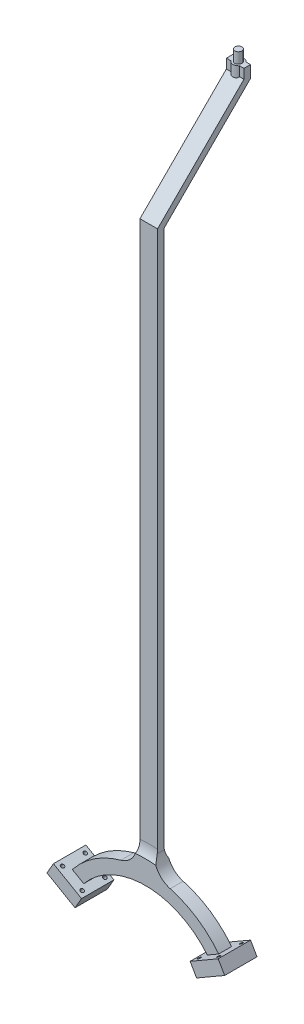
SolidWorks part; units mm, degrees
material "6063-T5"
ref_plane "Front Plane" through (0, 0, 0) normal (0, 0, 1) x (1, 0, 0)
ref_plane "Top Plane" through (0, 0, 0) normal (0, 1, 0) x (1, 0, 0)
ref_plane "Right Plane" through (0, 0, 0) normal (1, 0, 0) x (0, 0, -1)
sketch "Sketch1" plane through (0, 0, 0) normal (0, 1, 0) x (1, 0, 0)
  circle A0 centre (0, 0) radius 8.2
  dimension "D1" = 16.4
extrude "Boss-Extrude1" add sketch "Sketch1" along normal blind 25 contours A0
sketch "Sketch2" plane through (0, 0, 0) normal (0, -1, 0) x (-1, 0, 0)
  line L0 (-20.395, -7.5) -> (20.395, -7.5)
  line L1 (-20.395, -7.5) -> (-20.395, 7.5)
  line L2 (20.395, -7.5) -> (20.395, 7.5)
  line L3 (-20.395, 7.5) -> (20.395, 7.5)
  line L4 (-20.395, -7.5) -> (20.395, 7.5) construction
  line L5 (20.395, -7.5) -> (-20.395, 7.5) construction
  point P1 (0, 0)
  dimension "D1" = 40.79
  dimension "D2" = 15
extrude "Boss-Extrude2" add sketch "Sketch2" along normal blind 25
sketch "Sketch3" plane through (0, -25, 0) normal (0, -1, 0) x (-1, 0, 0)
  circle A0 centre (0, 0) radius 12.5
  dimension "D1" = 25
extrude "Boss-Extrude4" add sketch "Sketch3" against normal up to surface (25 mm away) up to face at (-13.0763, 0, 0)
sketch "Sketch4" plane through (-20.395, 0, 0) normal (-1, 0, 0) x (0, 0, 1)
  line L0 (7.5, -25) -> (207.5, -25)
  line L1 (207.5, -25) -> (207.5, -225)
  line L2 (207.5, -225) -> (7.5, -25)
  line L3 (207.5, -225) -> (192.5, -225)
  line L5 (192.5, -225) -> (-7.5, -25)
  line L6 (-7.5, -25) -> (7.5, -25)
  line M7 (-7.5, -25) -> (7.5, -25)
  dimension "D1" = 200
  dimension "D2" = 200
  dimension "D3" = 15
extrude "Boss-Extrude5" add sketch "Sketch4" against normal up to surface (40.79 mm away) contours L5 L3 L2 M7 region at (-20.395, -125, 100) up to face at (20.395, -12.5, 0)
sketch "Sketch5" plane through (0, -225, 0) normal (0, -1, 0) x (-1, 0, 0)
  line L1 (-20.395, -207.5) -> (20.395, -207.5)
  line L2 (-20.395, -207.5) -> (-20.395, -192.5)
  line L3 (-20.395, -192.5) -> (20.395, -192.5)
  line L4 (20.395, -207.5) -> (20.395, -192.5)
extrude "Boss-Extrude7" add sketch "Sketch5" along normal blind 1505
sketch "Sketch7" plane through (20.395, 0, 0) normal (1, 0, 0) x (0, 0, -1)
  line L0 (-7.5, -25) -> (0, -32.5)
  line L1 (7.5, -25) -> (-192.5, -225) construction
  line L2 (0, -32.5) -> (1.5521, -34.0521)
  line L3 (-7.5, -25) -> (-9.0521, -23.4479)
  line L4 (-9.0521, -23.4479) -> (-7.5, -21.8958)
  line L5 (-7.5, -25) -> (-7.5, 0) construction
  line L6 (1.5521, -34.0521) -> (7.5, -28.1042)
  line L7 (7.5, -28.1042) -> (7.5, -25)
  line L8 (1.5521, -34.0521) -> (-192.5, -228.1042)
  line L9 (-192.5, -1730) -> (-192.5, -225) construction
  line L10 (-192.5, -228.1042) -> (-192.5, -225)
  line L11 (-192.5, -225) -> (7.5, -25)
  line L12 (-9.0521, -23.4479) -> (-207.5, -221.8958)
  line L13 (-207.5, -221.8958) -> (-207.5, -225)
  line L14 (-207.5, -225) -> (-7.5, -25)
  line L15 (-7.5, -21.8958) -> (-7.5, -25)
  line M3 (-7.5, 0) -> (-7.5, -25)
  line M4 (-7.5, -25) -> (-207.5, -225)
  line M6 (-192.5, -225) -> (7.5, -25)
  line M12 (-192.5, -1730) -> (-192.5, -225)
  dimension "D1" = 10.6066
  dimension "D2" = 2.195
  dimension "D3" = 2.195
extrude "Boss-Extrude8" add sketch "Sketch7" against normal up to surface (40.79 mm away) contours L8 L2 M6 M12 | L6 L7 L2 M6 | L12 L13 L3 M4 | L4 L3 M3 region at (20.395, -29.8693, -4.1231) region at (20.395, -129.9156, 95.8615) region at (20.395, -123.8374, 107.8875) region at (20.395, -23.4479, 8.0174) up to face at (-20.395, -495, 100)
ref_plane "Plane4" through (0, 0, 0) normal (1, 0, 0) x (0, 0, -1)
ref_axis "Axis1" through (0, -1730, 192.5) along (0, 0, 1)
sketch "Sketch9" plane through (0, 0, 0) normal (1, 0, 0) x (0, 0, -1)
  line L0 (0, 0) -> (0, -1530)
  line L1 (0, -1530) -> (-200, -1530)
  line L2 (-200, -1530) -> (-200, -1515)
  line L3 (-200, -1515) -> (-185, -1515)
  line L4 (-200, -1530) -> (-215, -1530)
  line L5 (-215, -1530) -> (-215, -1545)
  line L7 (-215, -1545) -> (-185, -1545)
  line L8 (-215, -1545) -> (-215, -1515)
  line L9 (-215, -1515) -> (-185, -1515)
  line L10 (-185, -1545) -> (-185, -1515)
  dimension "D1" = 1530
  dimension "D2" = 200
  dimension "D3" = 15
  dimension "D4" = 15
  dimension "D5" = 15
  dimension "D6" = 15
revolve "Revolve1" add sketch "Sketch9" angle 60 about axis through (0, -1730, 192.5) along (0, 0, 1) region at (0, -1537.5, 200) region at (0, -1522.5, 192.5) region at (0, -1522.5, 207.5) other way angle 60
fillet "Fillet3" radius 50 4 edges at (20.395, -1515.9695, 200) (-20.395, -1515.9695, 200) (0, -1515, 192.5) (0, -1515, 207.5) type face fillet first side face at (0, -1568.75, 200) second side face at (-20.395, -441.4924, 100) second side face at (0, -868.6903, 207.5) second side face at (20.395, -441.4924, 100) second side face at (0, -871.7945, 192.5)
sketch "Sketch11" plane through (749.112, -1297.5, 0) normal (0.5, -0.866, 0) x (-0.866, -0.5, 0)
  line L0 (665, -185) -> (665, -215)
  line L1 (680, -185) -> (650, -185) construction
  line L2 (680, -215) -> (650, -215) construction
  line L3 (627.5, -237.5) -> (702.5, -237.5)
  line L4 (627.5, -237.5) -> (627.5, -162.5)
  line L5 (702.5, -237.5) -> (702.5, -162.5)
  line L6 (627.5, -162.5) -> (702.5, -162.5)
  line L7 (627.5, -237.5) -> (702.5, -162.5) construction
  line L8 (702.5, -237.5) -> (627.5, -162.5) construction
  line L9 (665, -200) -> (650, -185)
  line L10 (650, -185) -> (627.5, -162.5)
  circle A0 centre (638.75, -173.75) radius 4
  circle A1 centre (691.25, -173.75) radius 4
  circle A2 centre (691.25, -226.25) radius 4
  circle A3 centre (638.75, -226.25) radius 4
  point P7 (665, -200)
  point P25 (665, -200)
  line M1 (650, -185) -> (650, -215)
  line M2 (650, -215) -> (680, -215)
  line M3 (680, -215) -> (680, -185)
  line M4 (680, -185) -> (650, -185)
  dimension "D3" = 8
  dimension "D1" = 75
  dimension "D2" = 75
  dimension "D4" = 4
extrude "Boss-Extrude9" add sketch "Sketch11" against normal blind 30 contours A0 L4 L3 L5 L6 A3 A2 A1 M4 M3 M2 M1 | L0 L9 M1 M2 | L9 L0 M4 | L0 M4 M2 M3 region at (166.7099, -1633.75, 200) region at (173.2051, -1630, 163.5607) region at (177.5352, -1627.5, 190) region at (180.422, -1625.8333, 203.3333)
mirror "Mirror1" about plane through (0, 0, 0) normal (1, 0, 0) of "Boss-Extrude9"
sketch "Sketch15" plane through (0, 0, 192.5) normal (0, 0, -1) x (-1, 0, 0)
  line L0 (-20.395, -1730) -> (-20.395, -1546.1276)
  line L1 (20.395, -1546.1276) -> (20.395, -1730)
  line L2 (20.395, -1730) -> (-20.395, -1730)
  arc A0 (-20.395, -1546.1276) -> (20.395, -1546.1276) centre (0, -1730) cw
extrude "Cut-Extrude2" cut sketch "Sketch15" against normal through all
